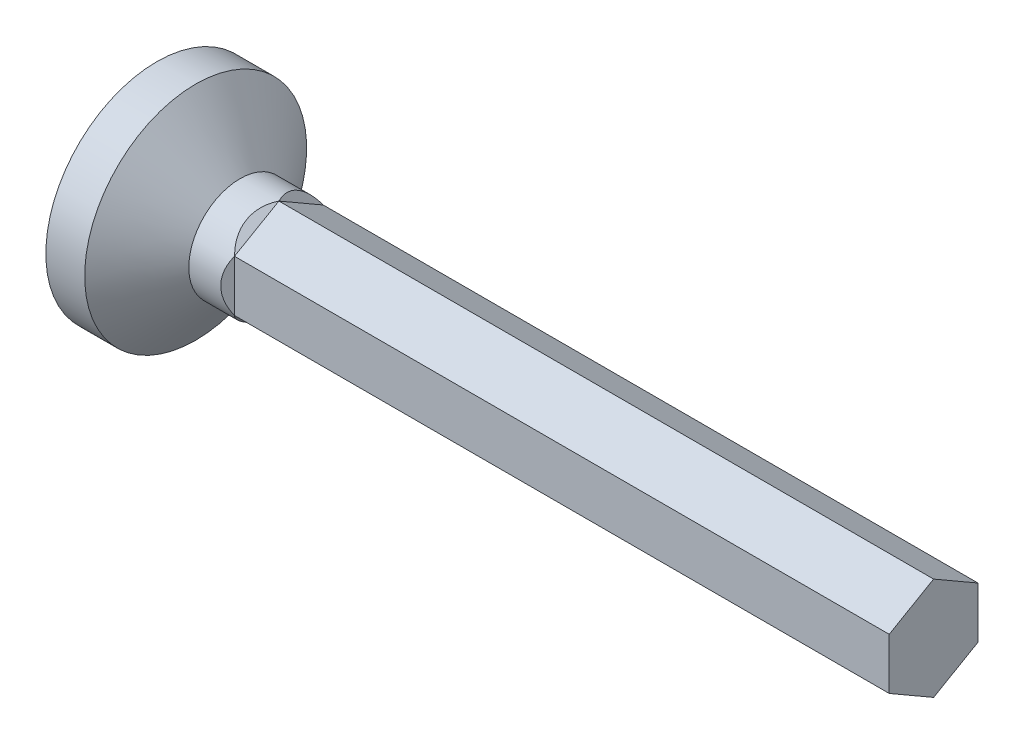
SolidWorks part; units mm, degrees
ref_plane "Front Plane" through (0, 0, 0) normal (0, 0, 1) x (1, 0, 0)
ref_plane "Top Plane" through (0, 0, 0) normal (0, 1, 0) x (1, 0, 0)
ref_plane "Right Plane" through (0, 0, 0) normal (1, 0, 0) x (0, 0, -1)
sketch "Sketch1" plane through (0, 0, 0) normal (1, 0, 0) x (0, 0, -1)
  line L1 (0, 2.3094) -> (-2, 1.1547)
  line L2 (-2, 1.1547) -> (-2, -1.1547)
  line L3 (-2, -1.1547) -> (0, -2.3094)
  line L4 (0, -2.3094) -> (2, -1.1547)
  line L5 (2, -1.1547) -> (2, 1.1547)
  line L6 (2, 1.1547) -> (0, 2.3094)
extrude "Boss-Extrude1" add sketch "Sketch1" along normal blind 30
sketch "Sketch4" plane through (0, 0, 0) normal (0, 0, 1) x (1, 0, 0)
  line L0 (0, 0) -> (-5, 0)
  line L1 (-5, 0) -> (-5, 5)
  line L2 (-5, 5) -> (-3.25, 5)
  line L3 (0, 2.3094) -> (-1.25, 2.3094)
  line L4 (-3.25, 5) -> (-1.25, 2.3094)
  line L5 (0, 2.3094) -> (0, 0)
sketch "Sketch5" plane through (0, 0, 0) normal (-1, 0, 0) x (0, 0, 1)
  circle A0 centre (0, 0) radius 2
revolve "Revolve4" add sketch "Sketch4" angle 360 about L0
chamfer "Chamfer1" distance 0.5 angle 45 2 edges at (0, -1.7321, -1) (0, 1.7321, 1)
chamfer "Chamfer2" distance 0.5 angle 45 2 edges at (0, 0, -2) (0, 0, 2)
chamfer "Chamfer3" distance 0.5 angle 45 2 edges at (0, 1.7321, -1) (0, -1.7321, 1)
